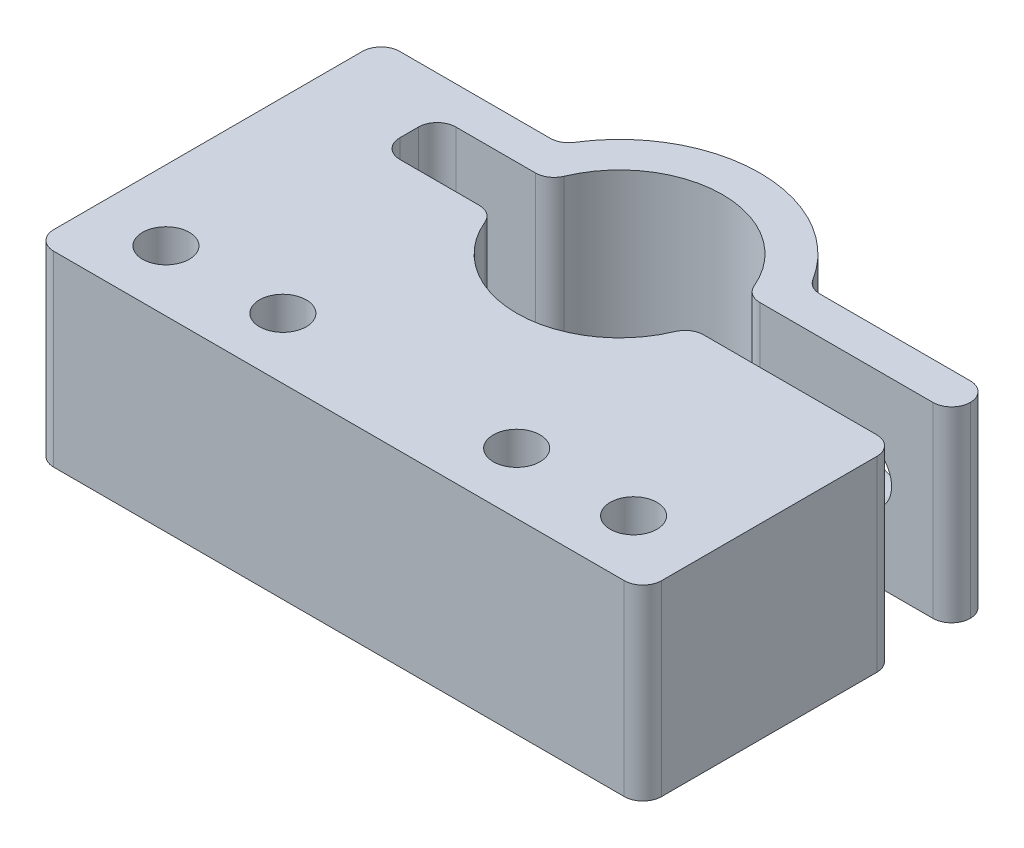
SolidWorks part; units mm, degrees
ref_plane "Front Plane" through (0, 0, 0) normal (0, 0, 1) x (1, 0, 0)
ref_plane "Top Plane" through (0, 0, 0) normal (0, 1, 0) x (1, 0, 0)
ref_plane "Right Plane" through (0, 0, 0) normal (1, 0, 0) x (0, 0, -1)
sketch "Sketch1" plane through (0, 0, 0) normal (0, 1, 0) x (1, 0, 0)
  line L1 (-32.5, 30) -> (32.5, 30)
  line L2 (-32.5, 30) -> (-32.5, -30)
  line L3 (-32.5, -30) -> (32.5, -30)
  line L4 (32.5, 30) -> (32.5, -30)
  line L5 (-32.5, 30) -> (32.5, -30) construction
  line L6 (-32.5, -30) -> (32.5, 30) construction
  circle A0 centre (0, 0) radius 11
  point P0 (0, 0)
  dimension "D1" = 22
  dimension "D2" = 65
  dimension "D3" = 60
extrude "Boss-Extrude1" add sketch "Sketch1" along normal blind 20
sketch "Sketch2" plane through (0, 20, 0) normal (0, 1, 0) x (1, 0, 0)
  line L0 (-32.5, 0) -> (32.5, 0) construction
  line L1 (-32.5, 30) -> (-32.5, -30) construction
  line L2 (32.5, -30) -> (32.5, 30) construction
  line L3 (32.5, 3) -> (-22.5, 3)
  line L4 (-22.5, 3) -> (-22.5, -3)
  line L5 (-22.5, -3) -> (32.5, -3)
  point P8 (0, 0)
  dimension "D1" = 6
  dimension "D2" = 22.5
extrude "Cut-Extrude1" cut sketch "Sketch2" against normal through all and the other way through all
sketch "Sketch3" plane through (0, 20, 0) normal (0, 1, 0) x (1, 0, 0)
  line L0 (-32.5, -23.5) -> (32.5, -23.5) construction
  line L1 (-32.5, 30) -> (-32.5, -30) construction
  line L2 (32.5, -30) -> (32.5, -3) construction
  line L4 (0, 0) -> (0, -23.5) construction
  circle A0 centre (0, 0) radius 20 construction
  circle A1 centre (12.5, -23.5) radius 6.5 construction
  circle A2 centre (25, -23.5) radius 12.7 construction
  point P11 (12.5, -23.5)
  point P14 (25, -23.5)
  dimension "D2" = 40
  dimension "D4" = 13
  dimension "D6" = 25.4
  dimension "D1" = 23.5
  dimension "D3" = 12.5
  dimension "D5" = 12.5
hole_wizard "M6 Tapped Hole2" positions "Sketch4" profile "Sketch5" tap size "M6" standard "ISO" end condition through all
sketch "Sketch4" plane through (0, 20, 0) normal (0, 1, 0) x (1, 0, 0)
  point P4 (12.5, -23.5)
sketch "Sketch5" plane through (12.5, 20, 23.5) normal (1, 0, 0) x (0, 0, 1)
  line L0 (0, 0) -> (0, 20)
  line L1 (0, 20) -> (2.5, 20)
  line L2 (2.5, 20) -> (2.5, 0)
  line L5 (2.5, 0) -> (0, 0)
  line L11 (0, -6.35) -> (0, 107.95) construction
  dimension "Thread Major Dia." = 5
  dimension "Thru Tap Drill Depth" = 20
pattern_linear "LPattern2" count 2 spacing 12.5 along (1, 0, 0) of "M6 Tapped Hole2"
mirror "Mirror2" about plane through (0, 0, 0) normal (1, 0, 0) of "LPattern2"
ref_plane "Plane1" through (0, 10, 0) normal (0, 1, 0) x (1, 0, 0)
sketch "Sketch6" plane through (0, 20, 0) normal (0, 1, 0) x (1, 0, 0)
  line L0 (-32.5, 7) -> (-13.2665, 7)
  line L1 (-32.5, 30) -> (-32.5, -30) construction
  line L2 (13.2665, 7) -> (32.5, 7)
  line L3 (32.5, 3) -> (32.5, 30) construction
  line L4 (10.583, 3) -> (32.5, 3) construction
  line L5 (-32.5, 7) -> (-32.5, 30)
  line L6 (-32.5, 30) -> (32.5, 30)
  line L7 (32.5, 30) -> (32.5, 7)
  arc A0 (-13.2665, 7) -> (13.2665, 7) centre (0, 0) cw
  dimension "D1" = 15
  dimension "D2" = 4
extrude "Cut-Extrude2" cut sketch "Sketch6" against normal through all
ref_plane "Plane2" through (13.2665, 0, 0) normal (1, 0, 0) x (0, 0, -1)
ref_plane "Plane3" through (22.8832, 0, 0) normal (1, 0, 0) x (0, 0, -1)
ref_plane "Plane4" through (0, 10, 0) normal (0, 1, 0) x (1, 0, 0)
ref_axis "Axis1" through (22.8832, 10, -6.2) along (0, 0, 1)
sketch "Sketch7" plane through (0, 0, -7) normal (0, 0, -1) x (-1, 0, 0)
  point P0 (-22.8832, 10)
hole_wizard "M6 Clearance Hole1" positions "Sketch8" profile "Sketch9" hole size "M6" standard "ISO" end condition up to next
sketch "Sketch8" plane through (0, 0, -7) normal (0, 0, -1) x (-1, 0, 0)
  point P0 (-22.8832, 10)
sketch "Sketch9" plane through (22.8832, 10, -7) normal (1, 0, 0) x (0, 1, 0)
  line L0 (0, 0) -> (0, 4)
  line L1 (0, 4) -> (3.2, 4)
  line L2 (3.2, 4) -> (3.2, 0)
  line L5 (3.2, 0) -> (0, 0)
  line L11 (0, -6.35) -> (0, 107.95) construction
  dimension "Thru Hole Dia." = 6.4
  dimension "Thru Hole Depth" = 4
ref_plane "Plane5" through (0, 0, -15) normal (0, 0, -1) x (-1, 0, 0)
sketch "Sketch10" plane through (0, 0, 3) normal (0, 0, -1) x (-1, 0, 0)
  point P0 (-22.8832, 10)
hole_wizard "M6 Tapped Hole1" positions "Sketch11" profile "Sketch13" tap size "M6" standard "ISO"
sketch "Sketch11" plane through (0, 0, 3) normal (0, 0, -1) x (-1, 0, 0)
  point P0 (-22.8832, 10)
sketch "Sketch13" plane through (22.8832, 10, 3) normal (1, 0, 0) x (0, 1, 0)
  line L0 (0, 0) -> (0, 11.5022)
  line L1 (0, 11.5022) -> (2.5, 10)
  line L2 (2.5, 10) -> (2.5, 0)
  line L5 (2.5, 0) -> (0, 0)
  line L10 (0, 11.5022) -> (-2.5, 10) construction
  line L11 (0, -6.35) -> (0, 107.95) construction
  dimension "Tap Drill Dia." = 5
  dimension "Tap Drill Depth" = 10
  dimension "Drill Angle" = 118
cosmetic thread "Hole Thread1" parameters "D1"=10, "D2"=6
fillet "Fillet1" radius 2 14 edges at (32.5, 10, 3) (10.583, 10, 3) (-10.583, 10, 3) (-22.5, 10, 3) (-22.5, 10, -3) (-10.583, 10, -3) (10.583, 10, -3) (32.5, 10, -3) (13.2665, 10, -7) (-13.2665, 10, -7) (32.5, 10, -7) (32.5, 10, 30) (-32.5, 10, -7) (-32.5, 10, 30)
